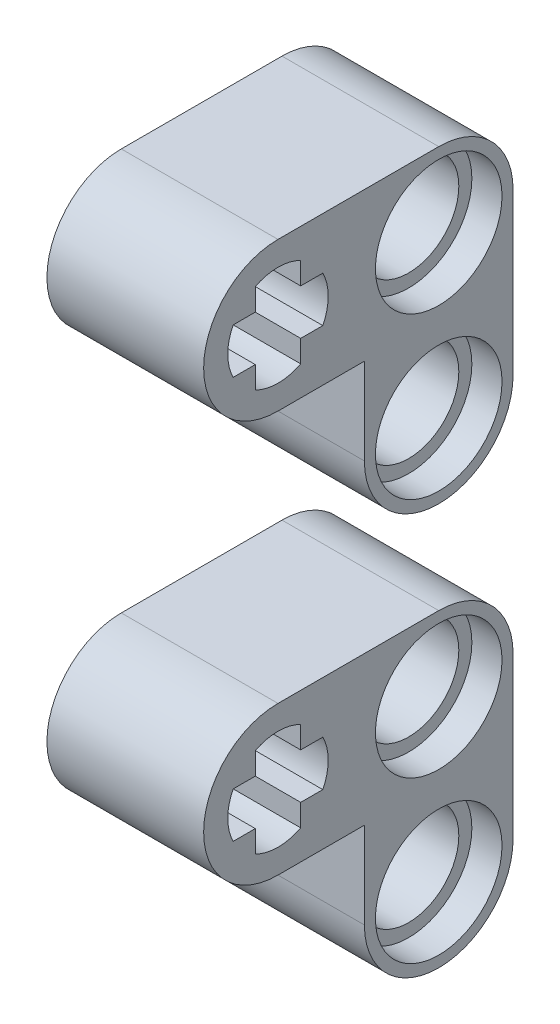
SolidWorks part; units mm, degrees
ref_plane "前视基准面" through (0, 0, 0) normal (0, 0, 1) x (1, 0, 0)
ref_plane "上视基准面" through (0, 0, 0) normal (0, 1, 0) x (1, 0, 0)
ref_plane "右视基准面" through (0, 0, 0) normal (1, 0, 0) x (0, 0, -1)
other "Configuration Table"
sketch "草图1" plane through (0, 0, 0) normal (1, 0, 0) x (0, 0, -1)
  line L0 (8, 0) -> (8, -8) construction
  line L2 (0, 0) -> (8, 0) construction
  line L3 (-2.23, 1.13) -> (-1.13, 1.13)
  line L4 (-1.13, -2.23) -> (1.13, -2.23)
  line L5 (-1.13, -2.23) -> (-1.13, 2.23)
  line L6 (-1.13, 2.23) -> (1.13, 2.23)
  line L7 (1.13, -2.23) -> (1.13, 2.23)
  line L8 (-1.13, -2.23) -> (1.13, 2.23) construction
  line L9 (-1.13, 2.23) -> (1.13, -2.23) construction
  line L10 (-2.23, -1.13) -> (2.23, -1.13)
  line L11 (-2.23, -1.13) -> (-2.23, 1.13)
  line L12 (-2.23, 1.13) -> (2.23, 1.13)
  line L13 (2.23, -1.13) -> (2.23, 1.13)
  line L14 (-2.23, -1.13) -> (2.23, 1.13) construction
  line L15 (-2.23, 1.13) -> (2.23, -1.13) construction
  line L17 (0, 3.7) -> (8, 3.7)
  line L18 (0, 3.7) -> (0, -3.7)
  line L19 (0, -3.7) -> (8, -3.7)
  line L20 (8, 3.7) -> (8, -3.7)
  line L21 (11.7, 0) -> (4.3, 0)
  line L22 (11.7, 0) -> (11.7, -8)
  line L23 (11.7, -8) -> (4.3, -8)
  line L24 (4.3, 0) -> (4.3, -8)
  line L26 (8, -11.7) -> (8, -4.3)
  circle A0 centre (0, 0) radius 2.5
  circle A1 centre (8, 0) radius 2.5
  circle A2 centre (8, 0) radius 3.15
  circle A3 centre (8, -8) radius 2.5
  circle A4 centre (8, -8) radius 3.15
  circle A7 centre (8, 0) radius 3.7
  circle A8 centre (8, -8) radius 3.7
  circle A10 centre (0, 0) radius 3.15
  circle A11 centre (0, 0) radius 3.7
  dimension "D1" = 5
  dimension "D2" = 6.3
  dimension "D3" = 7.4
  dimension "D4" = 8
  dimension "D5" = 1.1
extrude "凸台-拉伸1" add sketch "草图1" along normal blind 7.8 contours A11 | L17 L20 L19 L18 | A7 | L22 L23 L24 L21 | A8
extrude "切除-拉伸1" cut sketch "草图1<3>" along normal through all contours L23 A3 L26 | L26 A3 L23 | L26 A3 L23 | L23 A3 L26 | L21 A1 L20 | L20 A1 L21 | L21 A1 L20 | L20 A1 L21 | L6 A0 L18 | L18 A0 L6 | L11 A0 | L4 A0 L18 | L18 A0 L4 | L13 A0 | L5 L6 L7 L4 | L12 L13 L10 L11 region at (0, 0, 2.3385) region at (0, 2.3385, 0.427) region at (0, -2.3385, 0.427) region at (0, 2.3385, -0.427) region at (0, -2.3385, -0.427) region at (0, 0, -2.3385) region at (0, 1.061, -9.061) region at (0, 1.061, -6.939) region at (0, -1.061, -9.061) region at (0, -1.061, -6.939) region at (0, -6.939, -6.939) region at (0, -9.061, -6.939) region at (0, -9.061, -9.061) region at (0, -6.939, -9.061)
sketch "草图1<3>" plane through (0, 0, 0) normal (1, 0, 0) x (0, 0, -1) same geometry as "草图1"
extrude "切除-拉伸2" cut sketch "草图1<4>" along normal blind 1.5 contours L23 A4 L26 A3 | L26 A4 L23 A3 | L23 A4 L26 A3 | L26 A4 L23 A3 | L21 A2 L20 A1 | L20 A2 L21 A1 | L21 A2 L20 A1 | L20 A2 L21 A1 region at (0, 1.8064, -9.8064) region at (0, 1.8064, -6.1936) region at (0, -1.8064, -9.8064) region at (0, -1.8064, -6.1936) region at (0, -6.1936, -6.1936) region at (0, -9.8064, -6.1936) region at (0, -9.8064, -9.8064) region at (0, -6.1936, -9.8064)
sketch "草图1<4>" plane through (0, 0, 0) normal (1, 0, 0) x (0, 0, -1) same geometry as "草图1"
extrude "切除-拉伸3" cut sketch "草图1<5>" against normal blind 1.5 from surface contours L23 A4 L26 A3 | L26 A4 L23 A3 | L23 A4 L26 A3 | L26 A4 L23 A3 | L20 A2 L21 A1 | L21 A2 L20 A1 | L20 A2 L21 A1 | L21 A2 L20 A1 region at (0, 1.8064, -9.8064) region at (0, 1.8064, -6.1936) region at (0, -1.8064, -9.8064) region at (0, -1.8064, -6.1936) region at (0, -6.1936, -6.1936) region at (0, -9.8064, -6.1936) region at (0, -9.8064, -9.8064) region at (0, -6.1936, -9.8064) starting at face at (7.8, 0, -10.5)
sketch "草图1<5>" plane through (0, 0, 0) normal (1, 0, 0) x (0, 0, -1) same geometry as "草图1"
pattern_linear "阵列(线性)1" count 2 spacing 20 along (0, 1, 0) of bodies 109
